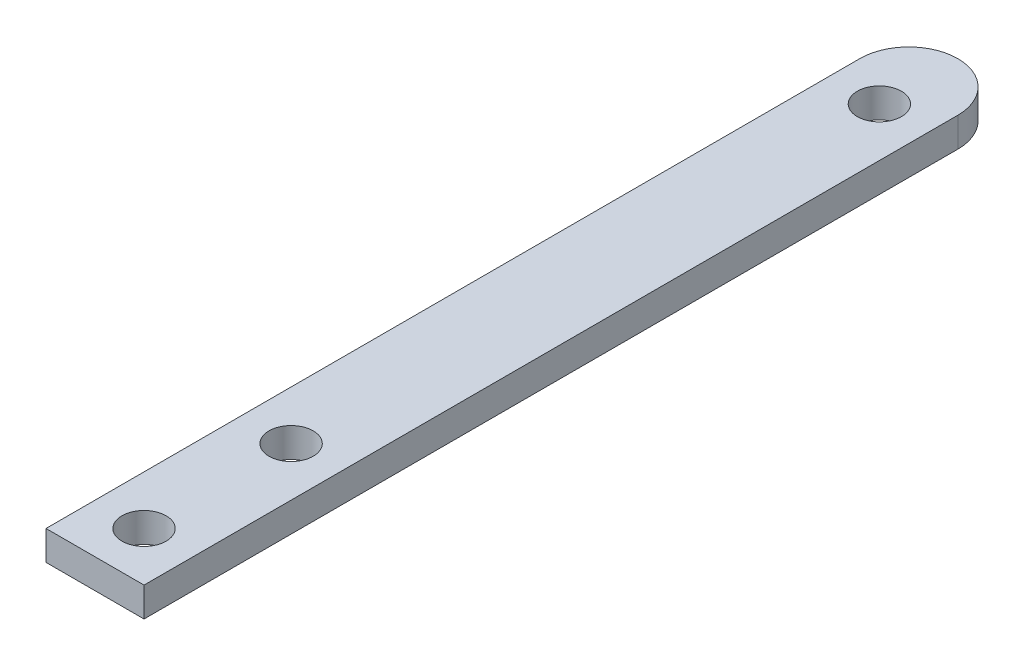
SolidWorks part; units mm, degrees
ref_plane "Front Plane" through (0, 0, 0) normal (0, 0, 1) x (1, 0, 0)
ref_plane "Top Plane" through (0, 0, 0) normal (0, 1, 0) x (1, 0, 0)
ref_plane "Right Plane" through (0, 0, 0) normal (1, 0, 0) x (0, 0, -1)
sketch "Sketch1" plane through (0, 0, 0) normal (0, 1, 0) x (1, 0, 0)
  line L0 (0, 0) -> (0, 88) construction
  line L1 (0, 0) -> (-5, 0)
  line L2 (-5, 0) -> (-5, 88)
  line L3 (-5, 88) -> (5, 88)
  line L4 (5, 88) -> (5, 0)
  line L5 (5, 0) -> (0, 0)
  circle A0 centre (0, 20) radius 2.25
  circle A1 centre (0, 5) radius 2.25
  circle A2 centre (0, 80) radius 2.25
  dimension "D1" = 4.5
  dimension "D2" = 10
  dimension "D3" = 15
  dimension "D4" = 5
  dimension "D5" = 8
  dimension "D6" = 60
extrude "Boss-Extrude1" add sketch "Sketch1" along normal blind 3
fillet "Fillet1" radius 5 2 edges at (5, 1.5, -88) (-5, 1.5, -88)
